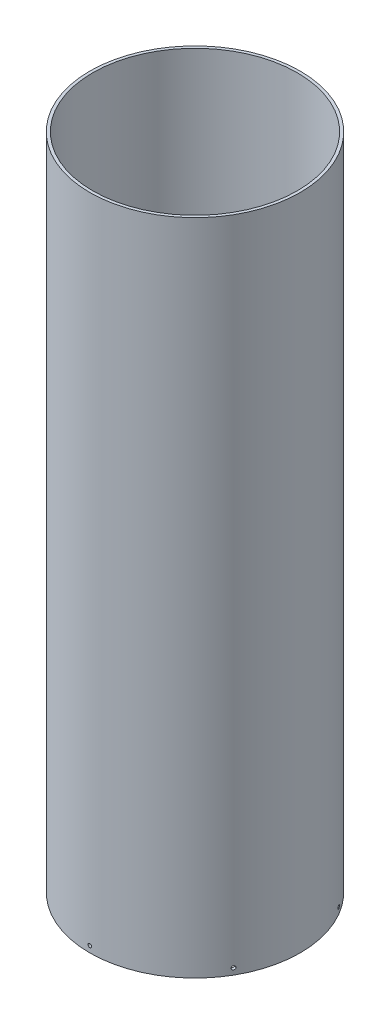
SolidWorks part; units mm, degrees
ref_plane "Front Plane" through (0, 0, 0) normal (0, 0, 1) x (1, 0, 0)
ref_plane "Top Plane" through (0, 0, 0) normal (0, 1, 0) x (1, 0, 0)
ref_plane "Right Plane" through (0, 0, 0) normal (1, 0, 0) x (0, 0, -1)
sketch "Sketch1" plane through (0, 0, 0) normal (0, 1, 0) x (1, 0, 0)
  circle A0 centre (0, 0) radius 76.2
  circle A1 centre (0, 0) radius 78.359
  dimension "D1" = 152.4
  dimension "D2" = 156.718
extrude "Boss-Extrude1" add sketch "Sketch1" along normal blind 490.5375
ref_axis "Axis1" through (0, 490.5375, 0) along (0, -1, 0)
sketch "Sketch2" plane through (0, 0, 0) normal (0, 0, 1) x (1, 0, 0)
  line L0 (0, 0) -> (0, 4.7625) construction
  circle A0 centre (0, 4.7625) radius 1.3526
  dimension "D1" = 2.7051
  dimension "D2" = 4.7625
extrude "Cut-Extrude1" cut sketch "Sketch2" against normal through all
pattern_circular "CirPattern1" count 6 over 360 about axis through (0, 490.5375, 0) along (0, -1, 0) of "Cut-Extrude1"
equation "\"D1@Boss-Extrude1\"=\"Aft_Upper_Length\""
equation "\"AB_Coupling_Section_Length\"= 0.375in"
equation "\"AB_Coupler_Num_Screws\"= 6"
equation "\"AB_Coupling_Screw_Diameter\"= 0.1065in"
equation "\"AB_Coupler_OD_Length\"= .6875in"
equation "\"AB_Coupler_Length\"= \"AB_Coupler_OD_Length\" + \"AB_Coupling_Section_Length\" * 2"
equation "\"D1@Sketch2\"=\"AB_Coupling_Screw_Diameter\""
equation "\"D2@Sketch2\"=\"AB_Coupling_Section_Length\"/2"
equation "\"D1@CirPattern1\"=\"AB_Coupler_Num_Screws\""
equation "\"Aft_Section_Length\"= 40in"
equation "\"Aft_Upper_Length\"= \"Aft_Section_Length\" - \"Aft_Lower_Length\" - \"AB_Coupler_OD_Length\""
equation "\"Aft_Lower_Length\"= 20in"
